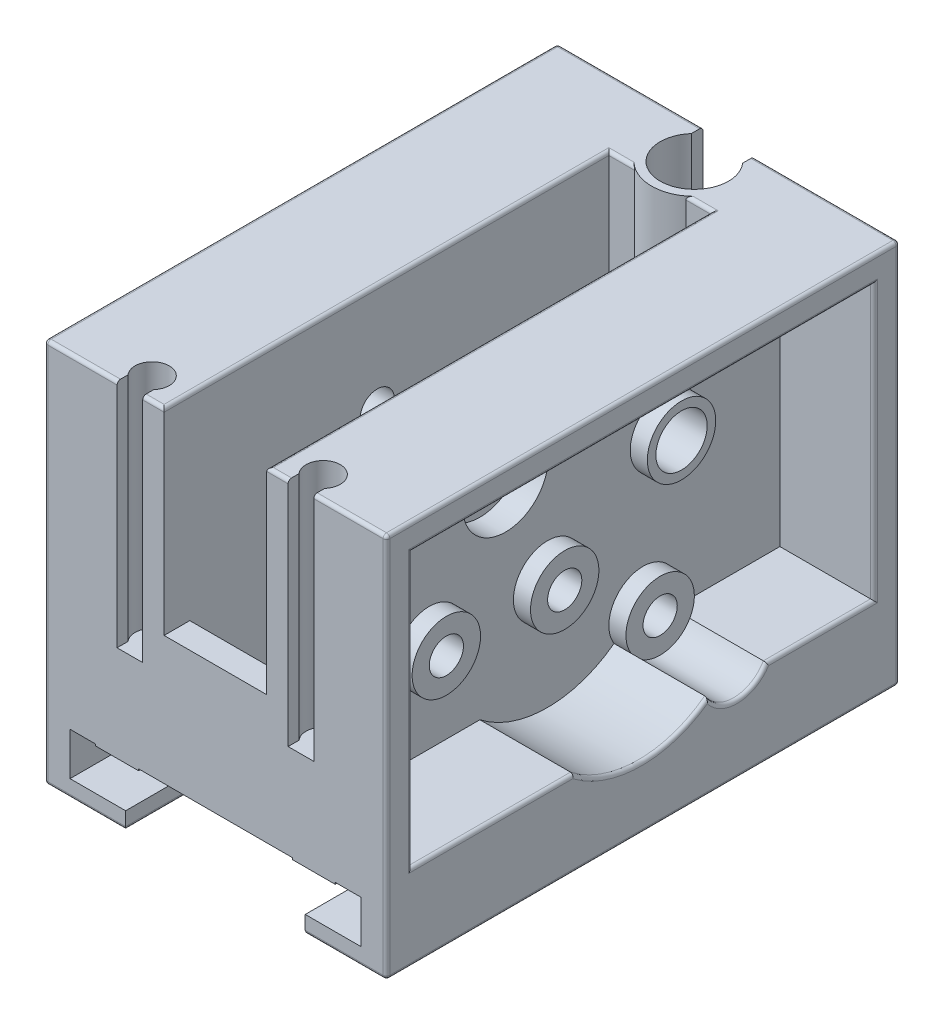
SolidWorks part; units mm, degrees
ref_plane "前视基准面" through (0, 0, 0) normal (0, 0, 1) x (1, 0, 0)
ref_plane "上视基准面" through (0, 0, 0) normal (0, 1, 0) x (1, 0, 0)
ref_plane "右视基准面" through (0, 0, 0) normal (1, 0, 0) x (0, 0, -1)
sketch "草图1" plane through (0, 0, 0) normal (0, 0, 1) x (1, 0, 0)
  line L1 (-10, 0) -> (10, 0)
  line L2 (-10, 0) -> (-10, 22.5)
  line L3 (-10, 22.5) -> (10, 22.5)
  line L4 (10, 0) -> (10, 22.5)
extrude "凸台-拉伸1" add sketch "草图1" against normal blind 30
sketch "草图2" plane through (0, 0, 0) normal (0, 0, 1) x (1, 0, 0)
  line L0 (-10, 0) -> (10, 0) construction
  line L1 (-5.25, 0) -> (5.25, 0)
  line L2 (-5.25, 0) -> (-5.25, 1)
  line L3 (5.25, 1) -> (8.5, 1)
  line L4 (5.25, 0) -> (5.25, 1)
  line L6 (-8.5, 1) -> (-5.25, 1)
  line L7 (-8.5, 1) -> (-8.5, 3.5)
  line L8 (-8.5, 3.5) -> (8.5, 3.5)
  line L9 (8.5, 1) -> (8.5, 3.5)
extrude "切除-拉伸1" cut sketch "草图2" against normal through all
sketch "草图3" plane through (0, 22.5, 0) normal (0, 1, 0) x (-1, 0, 0)
  line L0 (-1.5, -26) -> (-3, -26)
  line L1 (3, -1.5) -> (-3, -1.5)
  line L2 (3, -1.5) -> (3, -26)
  line L3 (3, -26) -> (1.5, -26)
  line L4 (-3, -1.5) -> (-3, -26)
  arc A0 (1.5, -26) -> (-1.5, -26) centre (0, -28) ccw
extrude "切除-拉伸2" cut sketch "草图3" against normal blind 18.5
sketch "草图4" plane through (0, 22.5, 0) normal (0, 1, 0) x (-1, 0, 0)
  line L0 (-10, -30) -> (10, -30) construction
  line L1 (1.5, -30) -> (-1.5, -30)
  line L2 (1.5, -30) -> (1.5, -29.3229)
  line L4 (-1.5, -30) -> (-1.5, -29.3229)
  arc A0 (1.5, -29.3229) -> (-1.5, -29.3229) centre (0, -28) ccw
extrude "切除-拉伸3" cut sketch "草图4" against normal blind 17
sketch "草图5" plane through (0, 22.5, 0) normal (0, 1, 0) x (-1, 0, 0)
  line L0 (-10, 0) -> (10, 0) construction
  line L1 (3, -1.5) -> (-3, -1.5)
  line L2 (3, -1.5) -> (3, 0)
  line L3 (3, 0) -> (-3, 0)
  line L4 (-3, -1.5) -> (-3, 0)
extrude "切除-拉伸4" cut sketch "草图5" against normal blind 11.5
sketch "草图6" plane through (0, 22.5, 0) normal (0, 1, 0) x (-1, 0, 0)
  line L0 (3, 0) -> (10, 0) construction
  line L1 (5.75, 0) -> (4.25, 0)
  line L2 (5.75, 0) -> (5.75, -0.6386)
  line L3 (-10, 0) -> (-3, 0) construction
  line L4 (4.25, 0) -> (4.25, -0.6386)
  line L5 (-4.25, 0) -> (-5.75, 0)
  line L6 (-4.25, 0) -> (-4.25, -0.6386)
  line L8 (-5.75, 0) -> (-5.75, -0.6386)
  arc A0 (4.25, -0.6386) -> (5.75, -0.6386) centre (5, -1.3) ccw
  arc A1 (-5.75, -0.6386) -> (-4.25, -0.6386) centre (-5, -1.3) ccw
extrude "切除-拉伸5" cut sketch "草图6" against normal blind 13.5
sketch "草图7" plane through (0, 3.5, 0) normal (0, -1, 0) x (1, 0, 0)
  line L0 (-10, -30) -> (-5.25, -30) construction
  line L1 (-7, -30) -> (-4.5, -30)
  line L2 (-7, -30) -> (-7, 0)
  line L3 (-7, 0) -> (-4.5, 0)
  line L4 (-4.5, -30) -> (-4.5, 0)
  line L5 (8.5, 0) -> (-8.5, 0) construction
  line L6 (8.5, -30) -> (-8.5, -30) construction
  line L7 (4.5, -30) -> (7, -30)
  line L8 (4.5, -30) -> (4.5, 0)
  line L9 (4.5, 0) -> (7, 0)
  line L10 (7, -30) -> (7, 0)
  line L11 (5.25, 0) -> (10, 0) construction
extrude "凸台-拉伸2" add sketch "草图7" along normal blind 0.1
sketch "草图8" plane through (0, 4, 0) normal (0, 1, 0) x (-1, 0, 0)
  line L1 (3, -26) -> (3, -1.5) construction
  line L2 (3, -25) -> (-3, -25)
  line L3 (3, -25) -> (3, -16)
  line L4 (3, -16) -> (-3, -16)
  line L6 (-3, -25) -> (-3, -16)
  line L7 (-3, -1.5) -> (-3, -26) construction
  line L8 (3, -26) -> (3, 0) construction
extrude "切除-拉伸6" cut sketch "草图8" against normal up to next
sketch "草图9" plane through (-10, 0, 0) normal (-1, 0, 0) x (0, 0, 1)
  line L0 (0, 22.5) -> (0, 0) construction
  circle A0 centre (-20.5, 6) radius 1
  circle A1 centre (-21.75, 14.25) radius 1.5
  circle A2 centre (-14.92, 10.09) radius 1
  circle A3 centre (-8, 10.22) radius 1
  circle A4 centre (-12.46, 16.25) radius 1
  dimension "D1" = 21.75
  dimension "D2" = 20.5
  dimension "D3" = 14.92
  dimension "D4" = 8
  dimension "D5" = 12.46
extrude "切除-拉伸7" cut sketch "草图9" against normal through all
sketch "草图11" plane through (-10, 0, 0) normal (-1, 0, 0) x (0, 0, 1)
  line L0 (-18.7679, 5) -> (-1.5, 5)
  line L2 (-1.5, 5) -> (-1.5, 21)
  line L3 (-1.5, 21) -> (-28.5, 21)
  line L4 (-28.5, 5) -> (-28.5, 21)
  line L5 (-28.5, 5) -> (-22.2321, 5)
  arc A0 (-22.2321, 5) -> (-18.7679, 5) centre (-20.5, 6) ccw
extrude "切除-拉伸9" cut sketch "草图11" against normal blind 5.5
sketch "草图12" plane through (10, 0, 0) normal (1, 0, 0) x (0, 0, -1)
  circle A0 centre (12.46, 16.25) radius 2.5
extrude "切除-拉伸10" cut sketch "草图12" against normal up to next
sketch "草图13" plane through (10, 0, 0) normal (1, 0, 0) x (0, 0, -1)
  line L1 (1.5, 5) -> (10.9584, 5)
  line L2 (1.5, 5) -> (1.5, 21)
  line L3 (1.5, 21) -> (28.5, 21)
  line L4 (28.5, 5) -> (28.5, 21)
  line L5 (22.2321, 5) -> (28.5, 5)
  arc A0 (10.9584, 5) -> (18.8038, 4.9404) centre (14.92, 10.09) ccw
  arc A1 (18.8038, 4.9404) -> (22.2321, 5) centre (20.5, 6) ccw
extrude "切除-拉伸11" cut sketch "草图13" against normal blind 5.5
sketch "草图14" plane through (0, 21, 0) normal (0, -1, 0) x (1, 0, 0)
  line L2 (-5.75, -0.6386) -> (-5.75, -0.3)
  line L4 (-4.25, -0.6386) -> (-4.25, -0.3)
  line L6 (4.25, -0.3) -> (4.25, -0.6386)
  line L8 (5.75, -0.3) -> (5.75, -0.6386)
  arc A0 (4.25, -0.6386) -> (5.75, -0.6386) centre (5, -1.3) ccw
  arc A1 (-5.75, -0.6386) -> (-4.25, -0.6386) centre (-5, -1.3) ccw
  arc A2 (-5.75, -0.3) -> (-4.25, -0.3) centre (-5, -1.3) ccw
  arc A3 (4.25, -0.3) -> (5.75, -0.3) centre (5, -1.3) ccw
extrude "凸台-拉伸3" add sketch "草图14" along normal blind 12.5
sketch "草图15" plane through (0, 8.5, 0) normal (0, 1, 0) x (-1, 0, 0)
  line L1 (-4.5, -1.5) -> (-4.5, -2.166)
  line L2 (-4.5, -1.5) -> (-5.9798, -1.5)
  line L3 (4.5, -1.5) -> (5.9798, -1.5)
  line L6 (4.5, -1.5) -> (4.5, -2.166)
  arc A0 (4.5, -2.166) -> (5.9798, -1.5) centre (5, -1.3) ccw
  arc A1 (-5.9798, -1.5) -> (-4.5, -2.166) centre (-5, -1.3) ccw
extrude "凸台-拉伸4" add sketch "草图15" along normal up to surface (0.5 mm away) up to face at (-4.9599, 9, -0.9251)
sketch "草图16" plane through (-4.5, 0, 0) normal (-1, 0, 0) x (0, 0, 1)
  circle A0 centre (-21.75, 14.25) radius 2
  circle A1 centre (-14.92, 10.09) radius 2
  circle A2 centre (-12.46, 16.25) radius 2
  circle A3 centre (-8, 10.22) radius 2
  circle A4 centre (-20.5, 6) radius 2
  circle A5 centre (-21.75, 14.25) radius 1.5
  circle A6 centre (-20.5, 6) radius 1
  circle A7 centre (-14.92, 10.09) radius 1
  circle A8 centre (-12.46, 16.25) radius 1
  circle A9 centre (-8, 10.22) radius 1
extrude "凸台-拉伸5" add sketch "草图16" along normal blind 1
sketch "草图17" plane through (4.5, 0, 0) normal (1, 0, 0) x (0, 0, -1)
  circle A0 centre (8, 10.22) radius 1
  circle A1 centre (8, 10.22) radius 2
  circle A2 centre (14.92, 10.09) radius 1
  circle A3 centre (14.92, 10.09) radius 2
  circle A4 centre (21.75, 14.25) radius 1.5
  circle A5 centre (21.75, 14.25) radius 2
  circle A6 centre (20.5, 6) radius 1
  circle A7 centre (20.5, 6) radius 2
extrude "凸台-拉伸6" add sketch "草图17" along normal blind 1
fillet "圆角1" radius 0.2 27 edges at (7.625, 0, -30) (7.625, 0, 0) (5.25, 0, -15) (-7.625, 0, -30) (-7.625, 0, 0) (-5.25, 0, -15) (-10, 0, -15) (-10, 11.25, -30) (-10, 22.5, -15) (-10, 11.25, 0) (-10, 21, -15) (-10, 13, -28.5) (-10, 5, -25.366) (-10, 4, -20.5) (-10, 5, -10.134) (-10, 13, -1.5) (10, 22.5, -15) (10, 11.25, -30) (10, 0, -15) (10, 11.25, 0) (10, 5, -6.2292) (10, 3.6402, -14.871) (10, 4.0003, -20.5348) (10, 5, -25.366) (10, 13, -28.5) (10, 21, -15) (10, 13, -1.5)
fillet "圆角2" radius 0.2 14 edges at (-9.9414, 22.4414, -29.9414) (9.9414, 22.4414, -29.9414) (9.9414, 22.4414, -0.0586) (-9.9414, 22.4414, -0.0586) (-5.65, 22.5, -30) (5.65, 22.5, -30) (2.25, 22.5, -26) (-2.25, 22.5, -26) (-3, 22.5, -13) (3, 22.5, -13) (7.775, 22.5, 0) (3.625, 22.5, 0) (-3.625, 22.5, 0) (-7.775, 22.5, 0)
sketch "草图18" plane through (0, 0, 0) normal (0, 0, 1) x (1, 0, 0)
  line L0 (-9.8, 0.2) -> (9.8, 0.2)
